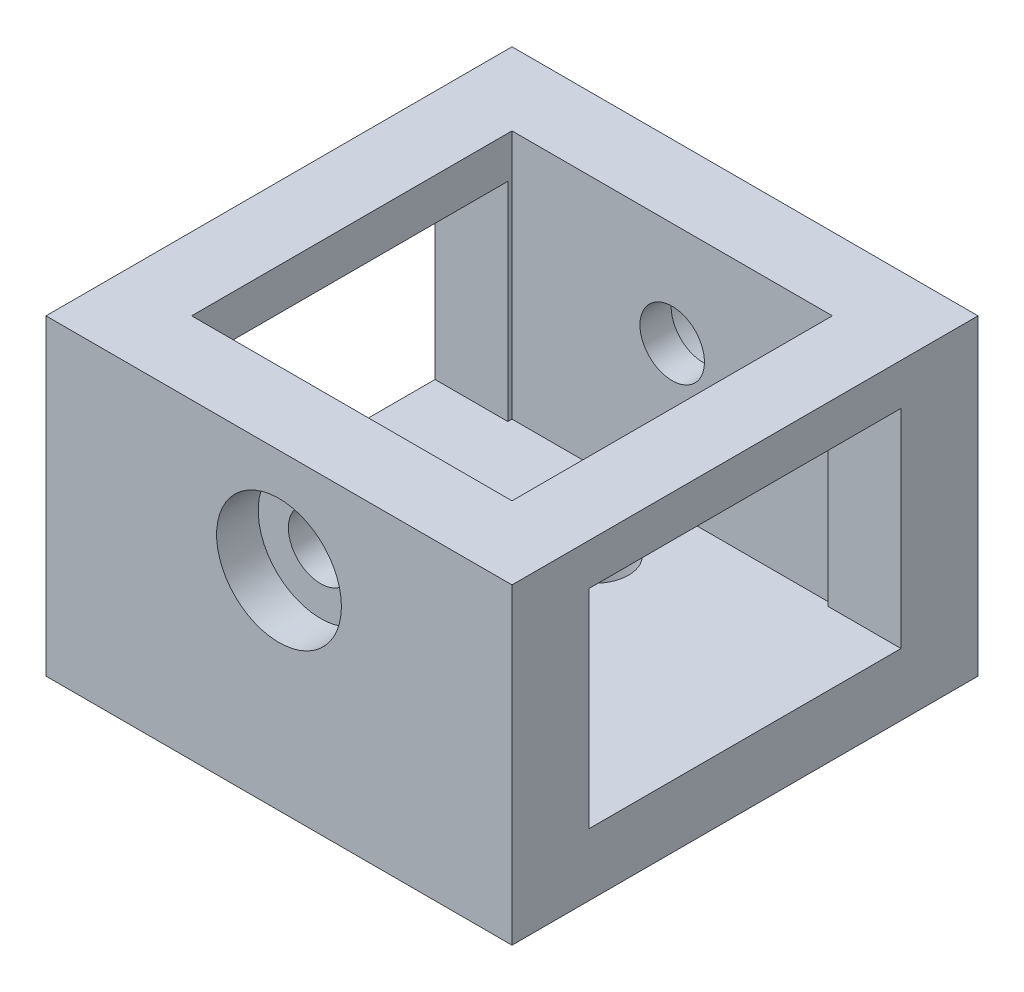
SolidWorks part; units mm, degrees
ref_plane "前视基准面" through (0, 0, 0) normal (0, 0, 1) x (1, 0, 0)
ref_plane "上视基准面" through (0, 0, 0) normal (0, 1, 0) x (1, 0, 0)
ref_plane "右视基准面" through (0, 0, 0) normal (1, 0, 0) x (0, 0, -1)
sketch "草图1" plane through (0, 0, 0) normal (0, 1, 0) x (1, 0, 0)
  line L0 (0, 0) -> (0, 7.7) construction
  line L1 (0, 0) -> (0, -7.7) construction
  line L2 (0, 0) -> (7.7, 0) construction
  line L3 (0, 0) -> (-7.7, 0) construction
  line L4 (0, 7.7) -> (7.7, 7.7)
  line L5 (7.7, 7.7) -> (7.7, 0)
  line L6 (7.7, -7.7) -> (0, -7.7)
  line L7 (-7.7, -7.7) -> (-7.7, 0)
  line L8 (-7.7, 7.7) -> (0, 7.7)
  line L9 (-7.7, 0) -> (-7.7, 7.7)
  line L10 (-7.7, -7.7) -> (0, -7.7)
  line L11 (7.7, -7.7) -> (7.7, 0)
  line L12 (-7.7, -7.7) -> (-7.7, -11.2)
  line L13 (7.7, -7.7) -> (7.7, -11.2)
  line L14 (-7.7, 11.2) -> (-7.7, 7.7)
  line L15 (7.7, 7.7) -> (7.7, 11.2)
  line L19 (-7.7, 11.2) -> (7.7, 11.2)
  line L22 (7.7, -11.2) -> (-7.7, -11.2)
  line L28 (-7.7, -7.7) -> (-4.7, -7.7)
  line L30 (7.7, 11.2) -> (11.2, 11.2)
  line L32 (11.2, 11.2) -> (11.2, -11.2)
  line L33 (7.7, -11.2) -> (11.2, -11.2)
  line L34 (-7.7, -11.2) -> (-11.2, -11.2)
  line L35 (-11.2, -11.2) -> (-11.2, 11.2)
  line L36 (-11.2, 11.2) -> (-7.7, 11.2)
extrude "凸台-拉伸2" add sketch "草图1" along normal blind 3 contours L6 L11 L5 L4 L8 L9 L7 L10 | L8 L4 | L6 L10 region at (0, 0, -9.45) region at (0, 0, 0) region at (0, 0, 9.45)
extrude "凸台-拉伸3" add sketch "草图1<4>" along normal blind 5 separate body contours L22 | L19 region at (0, 0, -9.45) region at (0, 0, 9.45)
sketch "草图1<4>" plane through (0, 0, 0) normal (0, 1, 0) x (1, 0, 0) same geometry as "草图1"
extrude "凸台-拉伸4" add sketch "草图1<5>" along normal blind 15 contours L36 L35 L34 L7 L9 | L33 L32 L30 L5 L11 | L10 | L6 | L4 | L8 region at (0, 0, -9.45) region at (9.45, 0, 0) region at (-9.45, 0, 0) region at (0, 0, 9.45)
sketch "草图1<5>" plane through (0, 0, 0) normal (0, 1, 0) x (1, 0, 0) same geometry as "草图1"
sketch "草图3" plane through (0, 0, -19.6) normal (0, 0, -1) x (-1, 0, 0)
  line L6 (0, 0) -> (0, 10) construction
  line L9 (17.5, 0) -> (-17.5, 0) construction
  circle A0 centre (0, 10) radius 1.55
  point P0 (0, 0)
extrude "切除-拉伸2" cut sketch "草图3" against normal through all contours A0 region at (0, 10, -19.6)
sketch "草图8" plane through (-11.2, 0, 0) normal (-1, 0, 0) x (0, 0, 1)
  line L0 (7.5, 10) -> (7.5, 3)
  line L1 (0, 3) -> (7.5, 3)
  line L2 (7.5, 10) -> (7.5, 13)
  line L3 (-7.5, 3) -> (0, 3)
  line L10 (-7.5, 3) -> (-7.5, 13)
  line L11 (-7.5, 13) -> (7.5, 13)
sketch "草图9" plane through (0, 0, 0) normal (0, -1, 0) x (1, 0, 0)
  line L0 (0, 0) -> (0, 4) construction
  line L1 (0, 0) -> (0, -4) construction
  circle A0 centre (0, 4) radius 1.6
  circle A1 centre (0, -4) radius 1.6
extrude "切除-拉伸6" cut sketch "草图9" against normal through all
sketch "草图10" plane through (0, 0, -11.2) normal (0, 0, -1) x (-1, 0, 0)
  circle A1 centre (0, 10) radius 3
extrude "切除-拉伸7" cut sketch "草图10" against normal blind 2
sketch "草图11" plane through (0, 0, 11.2) normal (0, 0, 1) x (1, 0, 0)
  circle A1 centre (0, 10) radius 3
extrude "切除-拉伸8" cut sketch "草图11" against normal blind 2
extrude "切除-拉伸9" cut sketch "草图8" against normal through all
